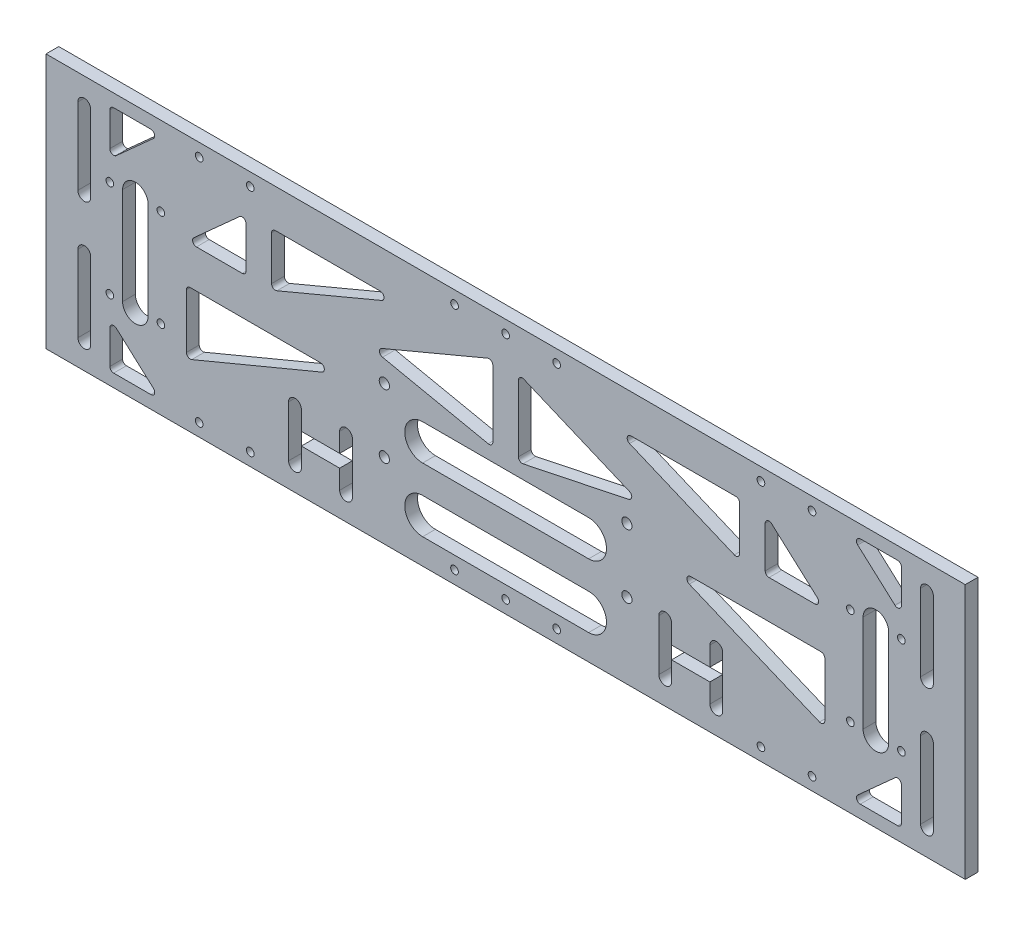
SolidWorks part; units mm, degrees
material "6061 合金"
ref_plane "前视基准面" through (0, 0, 0) normal (0, 0, 1) x (1, 0, 0)
ref_plane "上视基准面" through (0, 0, 0) normal (0, 1, 0) x (1, 0, 0)
ref_plane "右视基准面" through (0, 0, 0) normal (1, 0, 0) x (0, 0, -1)
sketch "草图1" plane through (0, 0, 0) normal (0, 0, 1) x (1, 0, 0)
  line L1 (0, 0) -> (320, 0)
  line L2 (0, 0) -> (0, 121)
  line L3 (0, 121) -> (320, 121)
  line L4 (320, 0) -> (320, 121)
  dimension "D1" = 320
  dimension "D2" = 121
extrude "凸台-拉伸1" add sketch "草图1" along normal blind 5
sketch "草图2" plane through (0, 0, 5) normal (0, 0, 1) x (1, 0, 0)
  line L0 (160, 121) -> (160, 0) construction
  line L1 (320, 121) -> (0, 121) construction
  line L2 (0, 0) -> (320, 0) construction
  line L3 (0, 121) -> (0, 0) construction
  line L4 (30, 0) -> (35, 0)
  line L5 (30, 0) -> (30, 30)
  line L6 (30, 30) -> (35, 30)
  line L7 (35, 0) -> (35, 30)
  line L8 (285, 0) -> (285, 30)
  line L9 (290, 30) -> (285, 30)
  line L10 (290, 0) -> (290, 30)
  line L11 (290, 0) -> (285, 0)
  dimension "D1" = 30
  dimension "D2" = 30
  dimension "D3" = 5
extrude "切除-拉伸1" cut sketch "草图2" against normal through all
sketch "草图3" plane through (0, 0, 5) normal (0, 0, 1) x (1, 0, 0)
  line L0 (40, 116) -> (60, 116) construction
  line L1 (160, 121) -> (160, 0) construction
  line L2 (320, 121) -> (0, 121) construction
  line L3 (35, 0) -> (285, 0) construction
  line L4 (140, 116) -> (160, 116) construction
  line L5 (0, 121) -> (0, 0) construction
  line L6 (280, 116) -> (260, 116) construction
  circle A0 centre (40, 116) radius 1.5
  circle A1 centre (60, 116) radius 1.5
  circle A2 centre (140, 116) radius 1.5
  circle A3 centre (160, 116) radius 1.5
  circle A4 centre (260, 116) radius 1.5
  circle A5 centre (280, 116) radius 1.5
  circle A6 centre (180, 116) radius 1.5
  dimension "D5" = 3
  dimension "D1" = 40
  dimension "D2" = 5
  dimension "D3" = 20
  dimension "D4" = 20
extrude "切除-拉伸2" cut sketch "草图3" against normal through all
sketch "草图4" plane through (0, 0, 5) normal (0, 0, 1) x (1, 0, 0)
  line L0 (160, 121) -> (160, 0) construction
  line L1 (5, 90) -> (25, 90) construction
  line L2 (5, 90) -> (5, 10) construction
  line L3 (5, 10) -> (25, 10) construction
  line L4 (25, 90) -> (25, 10) construction
  line L5 (320, 121) -> (0, 121) construction
  line L6 (35, 0) -> (285, 0) construction
  line L7 (0, 0) -> (30, 0) construction
  line L8 (0, 121) -> (0, 0) construction
  line L10 (295, 90) -> (295, 10) construction
  line L11 (315, 10) -> (295, 10) construction
  line L12 (315, 90) -> (315, 10) construction
  line L13 (315, 90) -> (295, 90) construction
  circle A0 centre (5, 90) radius 1.5
  circle A1 centre (25, 90) radius 1.5
  circle A2 centre (5, 10) radius 1.5
  circle A3 centre (25, 10) radius 1.5
  circle A4 centre (295, 10) radius 1.5
  circle A5 centre (315, 10) radius 1.5
  circle A6 centre (295, 90) radius 1.5
  circle A7 centre (315, 90) radius 1.5
  dimension "D5" = 3
  dimension "D1" = 10
  dimension "D2" = 80
  dimension "D3" = 5
  dimension "D4" = 20
extrude "切除-拉伸3" cut sketch "草图4" against normal through all
sketch "草图6" plane through (0, 0, 5) normal (0, 0, 1) x (1, 0, 0)
  line L0 (160, 121) -> (160, 0) construction
  line L1 (320, 121) -> (0, 121) construction
  line L2 (35, 0) -> (285, 0) construction
  line L3 (127.5, 63) -> (192.5, 63) construction
  line L4 (112.5, 50.5) -> (207.5, 50.5) construction
  line L5 (112.5, 50.5) -> (112.5, 75.5) construction
  line L6 (112.5, 75.5) -> (207.5, 75.5) construction
  line L7 (207.5, 50.5) -> (207.5, 75.5) construction
  line L8 (112.5, 50.5) -> (207.5, 75.5) construction
  line L9 (112.5, 75.5) -> (207.5, 50.5) construction
  line L10 (127.5, 70) -> (192.5, 70)
  line L11 (127.5, 56) -> (192.5, 56)
  circle A0 centre (112.5, 75.5) radius 2
  circle A1 centre (207.5, 75.5) radius 2
  circle A2 centre (207.5, 50.5) radius 2
  circle A3 centre (112.5, 50.5) radius 2
  arc A4 (127.5, 70) -> (127.5, 56) centre (127.5, 63) ccw
  arc A5 (192.5, 56) -> (192.5, 70) centre (192.5, 63) ccw
  point P6 (160, 63)
  point P17 (160, 63)
  dimension "D1" = 4
  dimension "D5" = 7
  dimension "D2" = 25
  dimension "D3" = 95
  dimension "D4" = 45.5
  dimension "D6" = 15
extrude "切除-拉伸5" cut sketch "草图6" against normal through all
sketch "草图5" plane through (0, 0, 5) normal (0, 0, 1) x (1, 0, 0)
  line L0 (5, 101.368) -> (5, 114.5)
  line L1 (6.5, 116) -> (21.0911, 116)
  line L2 (22.0945, 113.3851) -> (7.5034, 100.2531)
  line L6 (5, 90) -> (25, 90) construction
  line L7 (0, 121) -> (0, 0) construction
  line L8 (320, 121) -> (0, 121) construction
  line L9 (38.9089, 85) -> (56.8333, 85)
  line L10 (58.3333, 86.5) -> (58.3333, 102.632)
  line L11 (55.8299, 103.7469) -> (37.9055, 87.6149)
  line L12 (160, 121) -> (160, 0) construction
  line L13 (35, 0) -> (285, 0) construction
  line L14 (35, 68.5) -> (35, 47.25)
  line L15 (35, 0) -> (285, 0)
  line L16 (35, 0) -> (35, 30)
  line L17 (35, 30) -> (285, 30)
  line L18 (285, 0) -> (285, 30)
  line L19 (37.0769, 45.8654) -> (88.0769, 67.1154)
  line L20 (87.5, 70) -> (36.5, 70)
  line L24 (68.3333, 87.2569) -> (68.3333, 104.5)
  line L25 (69.8333, 106) -> (110.8883, 106)
  line L26 (111.4691, 103.117) -> (70.4142, 85.874)
  line L27 (111.7889, 84.0154) -> (153.1936, 75.3769)
  line L28 (155, 76.8453) -> (155, 102.8738)
  line L29 (152.9192, 104.2567) -> (111.5144, 86.8668)
  line L30 (315, 90) -> (295, 90) construction
  line L31 (167.0808, 104.2567) -> (208.4856, 86.8668)
  line L32 (165, 76.8453) -> (165, 102.8738)
  line L33 (208.2111, 84.0154) -> (166.8064, 75.3769)
  line L34 (208.5309, 103.117) -> (249.5858, 85.874)
  line L35 (250.1667, 106) -> (209.1117, 106)
  line L36 (251.6667, 87.2569) -> (251.6667, 104.5)
  line L40 (232.5, 70) -> (283.5, 70)
  line L41 (282.9231, 45.8654) -> (231.9231, 67.1154)
  line L42 (285, 68.5) -> (285, 47.25)
  line L43 (264.1701, 103.7469) -> (282.0945, 87.6149)
  line L44 (261.6667, 86.5) -> (261.6667, 102.632)
  line L45 (281.0911, 85) -> (263.1667, 85)
  line L46 (297.9055, 113.3851) -> (312.4966, 100.2531)
  line L47 (313.5, 116) -> (298.9089, 116)
  line L48 (315, 101.368) -> (315, 114.5)
  line L52 (192.5, 70) -> (127.5, 70) construction
  arc A2 (155, 102.8738) -> (152.9192, 104.2567) centre (153.5, 102.8738) ccw
  arc A4 (21.0911, 116) -> (22.0945, 113.3851) centre (21.0911, 114.5) cw
  arc A5 (5, 101.368) -> (7.5034, 100.2531) centre (6.5, 101.368) ccw
  arc A6 (5, 114.5) -> (6.5, 116) centre (6.5, 114.5) cw
  arc A7 (56.8333, 85) -> (58.3333, 86.5) centre (56.8333, 86.5) ccw
  arc A8 (38.9089, 85) -> (37.9055, 87.6149) centre (38.9089, 86.5) cw
  arc A9 (58.3333, 102.632) -> (55.8299, 103.7469) centre (56.8333, 102.632) ccw
  arc A10 (88.0769, 67.1154) -> (87.5, 70) centre (87.5, 68.5) ccw
  arc A11 (35, 47.25) -> (37.0769, 45.8654) centre (36.5, 47.25) ccw
  arc A12 (35, 68.5) -> (36.5, 70) centre (36.5, 68.5) cw
  arc A17 (153.1936, 75.3769) -> (155, 76.8453) centre (153.5, 76.8453) ccw
  arc A18 (111.7889, 84.0154) -> (111.5144, 86.8668) centre (112.0953, 85.4838) cw
  arc A19 (68.3333, 87.2569) -> (70.4142, 85.874) centre (69.8333, 87.2569) ccw
  arc A20 (68.3333, 104.5) -> (69.8333, 106) centre (69.8333, 104.5) cw
  arc A21 (110.8883, 106) -> (111.4691, 103.117) centre (110.8883, 104.5) cw
  arc A22 (209.1117, 106) -> (208.5309, 103.117) centre (209.1117, 104.5) ccw
  arc A23 (251.6667, 104.5) -> (250.1667, 106) centre (250.1667, 104.5) ccw
  arc A24 (251.6667, 87.2569) -> (249.5858, 85.874) centre (250.1667, 87.2569) cw
  arc A25 (208.2111, 84.0154) -> (208.4856, 86.8668) centre (207.9047, 85.4838) ccw
  arc A26 (166.8064, 75.3769) -> (165, 76.8453) centre (166.5, 76.8453) cw
  arc A30 (285, 68.5) -> (283.5, 70) centre (283.5, 68.5) ccw
  arc A31 (285, 47.25) -> (282.9231, 45.8654) centre (283.5, 47.25) cw
  arc A32 (231.9231, 67.1154) -> (232.5, 70) centre (232.5, 68.5) cw
  arc A33 (261.6667, 102.632) -> (264.1701, 103.7469) centre (263.1667, 102.632) cw
  arc A34 (281.0911, 85) -> (282.0945, 87.6149) centre (281.0911, 86.5) ccw
  arc A35 (263.1667, 85) -> (261.6667, 86.5) centre (263.1667, 86.5) cw
  arc A36 (315, 114.5) -> (313.5, 116) centre (313.5, 114.5) ccw
  arc A37 (315, 101.368) -> (312.4966, 100.2531) centre (313.5, 101.368) cw
  arc A38 (298.9089, 116) -> (297.9055, 113.3851) centre (298.9089, 114.5) ccw
  arc A39 (165, 102.8738) -> (167.0808, 104.2567) centre (166.5, 102.8738) cw
  point P23 (25, 116)
  point P26 (5, 98)
  point P29 (5, 116)
  point P40 (35, 85)
  point P43 (58.3333, 106)
  point P56 (95, 70)
  point P59 (35, 45)
  point P62 (35, 70)
  point P84 (155, 105.1307)
  point P87 (155, 75)
  point P90 (107.0698, 85)
  point P93 (68.3333, 85)
  point P96 (68.3333, 106)
  point P99 (118.3333, 106)
  point P156 (201.6667, 106)
  point P157 (251.6667, 106)
  point P158 (251.6667, 85)
  point P159 (212.9302, 85)
  point P160 (165, 75)
  point P161 (165, 105.1307)
  point P162 (285, 70)
  point P163 (285, 45)
  point P164 (225, 70)
  point P165 (261.6667, 106)
  point P166 (285, 85)
  point P167 (315, 116)
  point P168 (315, 98)
  point P169 (295, 116)
  point P186 (20, 15)
  point P189 (8, 15)
  point P192 (20, 25)
  point P202 (300, 25)
  point P203 (312, 15)
  point P204 (300, 15)
  dimension "D8" = 1.5
  dimension "D12" = 1.5
  dimension "D16" = 1.5
  dimension "D27" = 1.5
  dimension "D4" = 5
  dimension "D5" = 5
  dimension "D6" = 20
  dimension "D7" = 18
  dimension "D9" = 5
  dimension "D10" = 10
  dimension "D11" = 10
  dimension "D13" = 15
  dimension "D14" = 15
  dimension "D15" = 60
  dimension "D21" = 15
  dimension "D22" = 10
  dimension "D23" = 50
  dimension "D24" = 15
  dimension "D25" = 10
  dimension "D26" = 5
  dimension "D29" = 8
  dimension "D31" = 10
extrude "切除-拉伸4" cut sketch "草图5" against normal through all
sketch "草图7" plane through (0, 0, 0) normal (0, 0, -1) x (-1, 0, 0)
  line L0 (-290, 0) -> (-290, 30)
  line L1 (-290, 30) -> (-30, 30)
  line L2 (-30, 30) -> (-30, 0)
  line L3 (-30, 0) -> (-290, 0)
extrude "凸台-拉伸2" add sketch "草图7" against normal blind 5
sketch "草图8" plane through (0, 0, 0) normal (0, 0, -1) x (-1, 0, 0)
  line L0 (-320, 0) -> (-320, 21)
  line L1 (-320, 0) -> (-320, 121) construction
  line L2 (-320, 21) -> (0, 21)
  line L3 (0, 121) -> (0, 0) construction
  line L4 (0, 21) -> (0, 0)
  line L5 (0, 0) -> (-320, 0)
extrude "切除-拉伸6" cut sketch "草图8" against normal blind 5
sketch "草图9" plane through (0, 0, 0) normal (0, 0, -1) x (-1, 0, 0)
  line L0 (-160, 21) -> (-335, 21)
  line L1 (0, 21) -> (-320, 21) construction
  line L2 (-335, 21) -> (-335, 121)
  line L3 (-335, 121) -> (15, 121)
  line L4 (15, 121) -> (15, 21)
  line L5 (15, 21) -> (-160, 21)
  line L6 (0, 21) -> (0, 121)
  line L7 (-320, 21) -> (-320, 121)
extrude "凸台-拉伸3" add sketch "草图9" against normal blind 5 contours L0 L7 L3 L2 | L6 L5 L4 L3 region at (327.5, 71, 0) region at (-7.5, 71, 0)
sketch "草图10" plane through (0, 0, 0) normal (0, 0, -1) x (-1, 0, 0)
  line L0 (-335, 71) -> (-325, 71)
  line L1 (-335, 21) -> (-335, 121) construction
  line L2 (-325, 71) -> (-325, 121)
  line L3 (-335, 121) -> (15, 121) construction
  line L4 (-325, 71) -> (-325, 21)
  line L5 (15, 21) -> (-335, 21) construction
  line L6 (15, 71) -> (5, 71)
  line L7 (15, 121) -> (15, 21) construction
  line L8 (5, 71) -> (5, 121)
  line L9 (5, 71) -> (5, 21)
  line L10 (-325, 71) -> (-325, 81)
  line L11 (-325, 81) -> (-325, 111)
  line L12 (-325, 71) -> (-325, 61)
  line L13 (-325, 61) -> (-325, 31)
  line L14 (-325, 81) -> (-325, 111) construction
  line L15 (-327.5, 81) -> (-327.5, 111)
  line L16 (-322.5, 81) -> (-322.5, 111)
  line L17 (-325, 61) -> (-325, 31) construction
  line L18 (-322.5, 61) -> (-322.5, 31)
  line L19 (-327.5, 61) -> (-327.5, 31)
  line L20 (-160, 21) -> (-160, 121)
  line L21 (5, 61) -> (5, 31) construction
  line L22 (2.5, 61) -> (2.5, 31)
  line L23 (7.5, 61) -> (7.5, 31)
  line L24 (5, 81) -> (5, 111) construction
  line L25 (7.5, 81) -> (7.5, 111)
  line L26 (2.5, 81) -> (2.5, 111)
  arc A0 (-327.5, 81) -> (-322.5, 81) centre (-325, 81) ccw
  arc A1 (-322.5, 111) -> (-327.5, 111) centre (-325, 111) ccw
  arc A2 (-322.5, 61) -> (-327.5, 61) centre (-325, 61) ccw
  arc A3 (-327.5, 31) -> (-322.5, 31) centre (-325, 31) ccw
  arc A4 (2.5, 61) -> (7.5, 61) centre (5, 61) cw
  arc A5 (7.5, 31) -> (2.5, 31) centre (5, 31) cw
  arc A6 (7.5, 81) -> (2.5, 81) centre (5, 81) cw
  arc A7 (2.5, 111) -> (7.5, 111) centre (5, 111) cw
  point P20 (-325, 96)
  point P25 (-325, 46)
  point P34 (5, 46)
  point P41 (5, 96)
  dimension "D1" = 10
  dimension "D2" = 10
  dimension "D3" = 30
  dimension "D4" = 10
  dimension "D5" = 30
extrude "切除-拉伸7" cut sketch "草图10" against normal blind 5 contours L16 A1 L2 L10 A0 | L2 A1 L15 A0 L10 | L4 A3 L18 A2 L12 | L19 A3 L4 L12 A2 | A7 L8 A6 L25 | A7 L26 A6 L8 | A5 L23 A4 L9 | A5 L9 A4 L22 region at (326.2281, 96, 0) region at (323.7719, 96, 0) region at (323.7719, 46, 0) region at (326.2281, 46, 0) region at (-3.7719, 96, 0) region at (-6.2281, 96, 0) region at (-6.2281, 46, 0) region at (-3.7719, 46, 0)
sketch "草图13" plane through (0, 0, 0) normal (0, 0, -1) x (-1, 0, 0)
  line L12 (-192.5, 63) -> (-192.5, 38)
  line L13 (-127.5, 63) -> (-127.5, 38)
  line L14 (-192.5, 38) -> (-127.5, 38) construction
  line L15 (-192.5, 45) -> (-127.5, 45)
  line L16 (-192.5, 31) -> (-127.5, 31)
  line L18 (-305, 63.5) -> (-305, 83.5)
  line L19 (-305, 63.5) -> (-305, 48.5)
  line L23 (-160, 21) -> (-160, 121)
  line L24 (15, 21) -> (-335, 21) construction
  line L25 (-335, 121) -> (15, 121) construction
  arc A1 (-192.5, 45) -> (-192.5, 31) centre (-192.5, 38) ccw
  arc A2 (-127.5, 31) -> (-127.5, 45) centre (-127.5, 38) ccw
  point P16 (-160, 38)
  dimension "D1" = 25
  dimension "D3" = 15
  dimension "D2" = 25
  dimension "D4" = 20
extrude "切除-拉伸8" cut sketch "草图13" against normal blind 5 contours L16 A2 L15 L23 | A1 L16 L23 L15 | L16 A2 L15 A1 region at (179.031, 38, 0) region at (140.969, 38, 0)
sketch "草图15" plane through (0, 0, 0) normal (0, 0, -1) x (-1, 0, 0)
  line L0 (-313.5, 116) -> (-298.9089, 116)
  line L1 (-297.9055, 113.3851) -> (-312.4966, 100.2531)
  line L2 (-315, 114.5) -> (-315, 101.368)
  line L3 (-21.0911, 116) -> (-6.5, 116)
  line L4 (-5, 114.5) -> (-5, 101.368)
  line L5 (-7.5034, 100.2531) -> (-22.0945, 113.3851)
  line L6 (-335, 71) -> (15, 71)
  line L7 (-335, 21) -> (-335, 121) construction
  line L8 (15, 121) -> (15, 21) construction
  line L9 (-21.0911, 26) -> (-6.5, 26)
  line L10 (-5, 27.5) -> (-5, 40.632)
  line L11 (-7.5034, 41.7469) -> (-22.0945, 28.6149)
  line L12 (-315, 27.5) -> (-315, 40.632)
  line L13 (-313.5, 26) -> (-298.9089, 26)
  line L14 (-297.9055, 28.6149) -> (-312.4966, 41.7469)
  circle A0 centre (-280, 116) radius 1.5
  circle A1 centre (-260, 116) radius 1.5
  circle A2 centre (-180, 116) radius 1.5
  circle A3 centre (-160, 116) radius 1.5
  circle A4 centre (-140, 116) radius 1.5
  circle A5 centre (-60, 116) radius 1.5
  circle A6 centre (-40, 116) radius 1.5
  circle A7 centre (-25, 90) radius 1.5
  circle A8 centre (-5, 90) radius 1.5
  circle A9 centre (-315, 90) radius 1.5
  circle A10 centre (-295, 90) radius 1.5
  arc A11 (-315, 101.368) -> (-312.4966, 100.2531) centre (-313.5, 101.368) ccw
  arc A12 (-313.5, 116) -> (-315, 114.5) centre (-313.5, 114.5) ccw
  arc A13 (-297.9055, 113.3851) -> (-298.9089, 116) centre (-298.9089, 114.5) ccw
  arc A14 (-21.0911, 116) -> (-22.0945, 113.3851) centre (-21.0911, 114.5) ccw
  arc A15 (-5, 114.5) -> (-6.5, 116) centre (-6.5, 114.5) ccw
  arc A16 (-7.5034, 100.2531) -> (-5, 101.368) centre (-6.5, 101.368) ccw
  circle A17 centre (-25, 52) radius 1.5
  circle A18 centre (-5, 52) radius 1.5
  arc A19 (-5, 27.5) -> (-6.5, 26) centre (-6.5, 27.5) cw
  arc A20 (-7.5034, 41.7469) -> (-5, 40.632) centre (-6.5, 40.632) cw
  arc A21 (-21.0911, 26) -> (-22.0945, 28.6149) centre (-21.0911, 27.5) cw
  circle A22 centre (-40, 26) radius 1.5
  circle A23 centre (-60, 26) radius 1.5
  circle A24 centre (-140, 26) radius 1.5
  circle A25 centre (-160, 26) radius 1.5
  circle A26 centre (-180, 26) radius 1.5
  circle A27 centre (-260, 26) radius 1.5
  circle A28 centre (-280, 26) radius 1.5
  arc A29 (-313.5, 26) -> (-315, 27.5) centre (-313.5, 27.5) cw
  arc A30 (-297.9055, 28.6149) -> (-298.9089, 26) centre (-298.9089, 27.5) cw
  arc A31 (-315, 40.632) -> (-312.4966, 41.7469) centre (-313.5, 40.632) cw
  circle A32 centre (-295, 52) radius 1.5
  circle A33 centre (-315, 52) radius 1.5
extrude "切除-拉伸9" cut sketch "草图15" against normal through all contours A33 | A31 L12 A29 L13 A30 L14 | A32 | A28 | A27 | A26 | A25 | A24 | A23 | A22 | A21 L9 A19 L10 A20 L11 | A18 | A17 region at (11.5603, 31.9627, 0) region at (308.4397, 31.9627, 0) region at (25, 52, 0) region at (5, 52, 0) region at (40, 26, 0) region at (60, 26, 0) region at (140, 26, 0) region at (160, 26, 0) region at (180, 26, 0) region at (260, 26, 0) region at (280, 26, 0) region at (295, 52, 0) region at (315, 52, 0)
sketch "草图16" plane through (0, 0, 0) normal (0, 0, -1) x (-1, 0, 0)
  line L0 (-335, 71) -> (15, 71)
  line L1 (-335, 21) -> (-335, 121) construction
  line L2 (15, 121) -> (15, 21) construction
  line L3 (-315, 90) -> (-295, 90)
  line L4 (-315, 52) -> (-295, 52)
  line L5 (-305, 52) -> (-305, 90)
  line L6 (-305, 52) -> (-305, 90) construction
  line L7 (-310, 52) -> (-310, 90)
  line L8 (-300, 52) -> (-300, 90)
  line L9 (-160, 21) -> (-160, 121)
  line L10 (15, 21) -> (-335, 21) construction
  line L11 (-335, 121) -> (15, 121) construction
  line L12 (-15, 52) -> (-15, 90) construction
  line L13 (-10, 52) -> (-10, 90)
  line L14 (-20, 52) -> (-20, 90)
  arc A0 (-310, 52) -> (-300, 52) centre (-305, 52) ccw
  arc A1 (-300, 90) -> (-310, 90) centre (-305, 90) ccw
  arc A2 (-10, 52) -> (-20, 52) centre (-15, 52) cw
  arc A3 (-20, 90) -> (-10, 90) centre (-15, 90) cw
  point P16 (-305, 71)
  point P29 (-15, 71)
extrude "切除-拉伸10" cut sketch "草图16" against normal through all contours L4 L8 L0 L5 | L4 A0 | L7 L4 L5 L0 | L0 L8 L3 L5 | L7 L0 L5 L3 | L3 A1 | A2 L13 L0 L14 | A3 L14 L0 L13 region at (307.5, 80.5, 0) region at (307.5, 61.5, 0) region at (15, 82.4907, 0) region at (15, 59.5093, 0) region at (302.5, 80.5, 0) region at (302.5, 61.5, 0) region at (305, 49.8779, 0) region at (305, 92.1221, 0)
sketch "草图17" plane through (0, 0, 0) normal (0, 0, -1) x (-1, 0, 0)
  line L0 (-207.5, 50.5) -> (-257.5, 50.5)
  line L1 (-257.5, 50.5) -> (-257.5, 30.5)
  line L2 (-257.5, 30.5) -> (-207.5, 30.5)
  line L3 (-207.5, 30.5) -> (-207.5, 50.5)
  line L4 (-207.5, 40.5) -> (-257.5, 40.5)
  line L5 (-257.5, 50.5) -> (-247.5, 50.5)
  line L6 (-247.5, 50.5) -> (-247.5, 30.5)
  line L7 (-207.5, 50.5) -> (-217.5, 50.5)
  line L8 (-217.5, 50.5) -> (-217.5, 30.5)
  line L9 (-247.5, 50.5) -> (-242.5, 50.5)
  line L10 (-242.5, 50.5) -> (-242.5, 30.5)
  line L11 (-217.5, 50.5) -> (-222.5, 50.5)
  line L12 (-222.5, 50.5) -> (-222.5, 30.5)
  line L13 (-242.5, 50.5) -> (-242.5, 30.5) construction
  line L14 (-240, 50.5) -> (-240, 30.5)
  line L15 (-245, 50.5) -> (-245, 30.5)
  line L16 (-222.5, 50.5) -> (-222.5, 30.5) construction
  line L17 (-220, 50.5) -> (-220, 30.5)
  line L18 (-225, 50.5) -> (-225, 30.5)
  line L19 (-242.5, 40.5) -> (-222.5, 40.5) construction
  line L20 (-242.5, 43) -> (-222.5, 43)
  line L21 (-242.5, 38) -> (-222.5, 38)
  line L22 (-160, 21) -> (-160, 121)
  line L23 (15, 21) -> (-335, 21) construction
  line L24 (-335, 121) -> (15, 121) construction
  line L25 (-97.5, 50.5) -> (-97.5, 30.5) construction
  line L26 (-100, 50.5) -> (-100, 30.5)
  line L27 (-95, 50.5) -> (-95, 30.5)
  line L28 (-77.5, 40.5) -> (-97.5, 40.5) construction
  line L29 (-77.5, 43) -> (-97.5, 43)
  line L30 (-77.5, 38) -> (-97.5, 38)
  line L31 (-77.5, 50.5) -> (-77.5, 30.5) construction
  line L32 (-80, 50.5) -> (-80, 30.5)
  line L33 (-75, 50.5) -> (-75, 30.5)
  arc A0 (-240, 50.5) -> (-245, 50.5) centre (-242.5, 50.5) ccw
  arc A1 (-245, 30.5) -> (-240, 30.5) centre (-242.5, 30.5) ccw
  arc A2 (-220, 50.5) -> (-225, 50.5) centre (-222.5, 50.5) ccw
  arc A3 (-225, 30.5) -> (-220, 30.5) centre (-222.5, 30.5) ccw
  arc A4 (-242.5, 43) -> (-242.5, 38) centre (-242.5, 40.5) ccw
  arc A5 (-222.5, 38) -> (-222.5, 43) centre (-222.5, 40.5) ccw
  arc A6 (-100, 50.5) -> (-95, 50.5) centre (-97.5, 50.5) cw
  arc A7 (-95, 30.5) -> (-100, 30.5) centre (-97.5, 30.5) cw
  arc A8 (-77.5, 43) -> (-77.5, 38) centre (-77.5, 40.5) cw
  arc A9 (-97.5, 38) -> (-97.5, 43) centre (-97.5, 40.5) cw
  arc A10 (-80, 50.5) -> (-75, 50.5) centre (-77.5, 50.5) cw
  arc A11 (-75, 30.5) -> (-80, 30.5) centre (-77.5, 30.5) cw
  point P11 (-242.5, 40.5)
  point P20 (-222.5, 40.5)
  point P25 (-232.5, 40.5)
  point P40 (-97.5, 40.5)
  point P47 (-87.5, 40.5)
  point P54 (-77.5, 40.5)
  dimension "D1" = 20
extrude "切除-拉伸11" cut sketch "草图17" against normal through all contours A11 L33 A8 L30 L32 | A8 L29 L32 L30 | A10 L32 L29 A8 L33 | L32 L29 L27 L30 | A9 L30 L27 L29 | L26 A9 L29 L27 A6 | L30 A9 L26 A7 L27 | L10 L20 L14 L0 | A4 L10 L0 L15 | L0 A0 | L20 L14 L4 L18 | L20 L10 L4 L14 | L10 A4 L4 | L4 A4 L10 | L10 L21 L14 L4 | L14 L21 L18 L4 | L21 L10 L2 L14 | A4 L15 L2 L10 | L2 A1 | L2 A3 | A5 L12 L2 L17 | L21 L18 L2 L12 | L18 L21 L12 L4 | L12 A5 L4 | L4 A5 L12 | L20 L18 L4 L12 | L18 L20 L12 L0 | A5 L17 L11 L12 | L11 A2 L0 region at (221.2038, 46.4624, 0) region at (222.5, 51.561, 0) region at (223.75, 46.75, 0) region at (221.439, 39.439, 0) region at (221.2038, 34.5376, 0) region at (221.439, 41.561, 0) region at (223.75, 41.75, 0) region at (223.75, 39.25, 0) region at (222.5, 29.439, 0) region at (223.75, 34.25, 0) region at (241.25, 46.75, 0) region at (242.5, 51.561, 0) region at (232.5, 41.75, 0) region at (232.5, 39.25, 0) region at (243.7962, 46.4624, 0) region at (241.25, 41.75, 0) region at (241.25, 39.25, 0) region at (242.5, 29.439, 0) region at (241.25, 34.25, 0) region at (243.561, 41.561, 0) region at (243.7962, 34.5376, 0) region at (243.561, 39.439, 0) region at (97.5535, 47.6019, 0) region at (97.5535, 33.3981, 0) region at (97.2666, 40.5, 0) region at (87.5, 40.5, 0) region at (77.4465, 47.6019, 0) region at (77.7334, 40.5, 0) region at (77.4465, 33.3981, 0)
sketch "草图18" plane through (0, 0, 0) normal (0, 0, -1) x (-1, 0, 0)
  line L0 (-335, 21) -> (-340, 21)
  line L1 (-340, 21) -> (-340, 121)
  line L2 (-340, 121) -> (-335, 121)
  line L3 (-335, 121) -> (-335, 21)
  line L4 (15, 21) -> (20, 21)
  line L5 (20, 21) -> (20, 121)
  line L6 (20, 121) -> (15, 121)
  line L7 (15, 121) -> (15, 21)
extrude "凸台-拉伸4" add sketch "草图18" against normal blind 5
